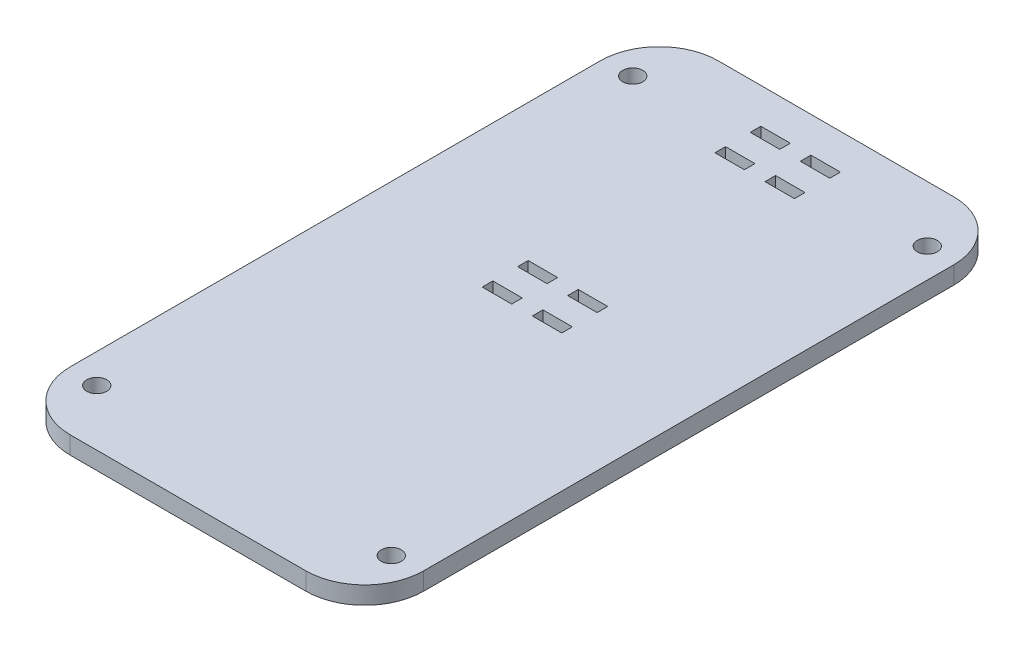
SolidWorks part; units mm, degrees
ref_plane "Front" through (0, 0, 0) normal (0, 0, 1) x (1, 0, 0)
ref_plane "Top" through (0, 0, 0) normal (0, 1, 0) x (1, 0, 0)
ref_plane "Right" through (0, 0, 0) normal (1, 0, 0) x (0, 0, -1)
sketch "Sketch1" plane through (0, 0, 0) normal (0, 1, 0) x (1, 0, 0)
  line L1 (-30, -55) -> (30, -55)
  line L2 (-30, -55) -> (-30, 55)
  line L3 (-30, 55) -> (30, 55)
  line L4 (30, -55) -> (30, 55)
  line L5 (-30, -55) -> (30, 55) construction
  line L6 (-30, 55) -> (30, -55) construction
  point P0 (0, 0)
  dimension "D1" = 60
  dimension "D2" = 110
extrude "Boss-Extrude1" add sketch "Sketch1" along normal blind 3
fillet "Fillet2" radius 10 4 edges at (-30, 1.5, 55) (30, 1.5, 55) (30, 1.5, -55) (-30, 1.5, -55)
sketch "Sketch2" plane through (0, 3, 0) normal (0, 1, 0) x (1, 0, 0)
  line L1 (-13, 31.5649) -> (13, 31.5649) construction
  line L2 (-13, 31.5649) -> (-13, -43.4351) construction
  line L3 (-13, -43.4351) -> (13, -43.4351) construction
  line L4 (13, 31.5649) -> (13, -43.4351) construction
  line L5 (-13, 31.5649) -> (13, -43.4351) construction
  line L6 (-13, -43.4351) -> (13, 31.5649) construction
  circle A0 centre (-13, -43.4351) radius 4.625 construction
  circle A1 centre (-13, 31.5649) radius 4.625
  circle A2 centre (13, 31.5649) radius 4.625
  circle A3 centre (-13, -43.4351) radius 4.625
  circle A4 centre (13, -43.4351) radius 4.625
  point P0 (0, -5.9351)
  dimension "D2" = 9.25
  dimension "D1" = 75
extrude "Cut-Extrude1" [suppressed] cut sketch "Sketch2" against normal through all
sketch "Sketch3" [suppressed] plane through (0, 3, 0) normal (0, 1, 0) x (1, 0, 0)
  circle A0 centre (13, 31.5649) radius 7.5
  circle A1 centre (-13, 31.5649) radius 7.5
  circle A2 centre (-13, -43.4351) radius 7.5
  circle A3 centre (13, -43.4351) radius 7.5
  circle A4 centre (-13, 31.5649) radius 4.625 construction
  circle A5 centre (13, 31.5649) radius 4.625 construction
  dimension "D1" = 15
extrude "Cut-Extrude2" [suppressed] cut sketch "Sketch3" against normal blind 1
hole_wizard "M3 Clearance Hole1" positions "Sketch5" profile "Sketch4" hole size "M3" standard "ANSI Metric" end condition through all
sketch "Sketch5" plane through (0, 3, 0) normal (0, 1, 0) x (1, 0, 0)
  line L1 (-25, -45.5) -> (25, -45.5)
  line L2 (-25, -45.5) -> (-25, 45.5)
  line L3 (-25, 45.5) -> (25, 45.5)
  line L4 (25, -45.5) -> (25, 45.5)
  line L5 (-25, -45.5) -> (25, 45.5) construction
  line L6 (-25, 45.5) -> (25, -45.5) construction
  point P1 (0, 0)
  point P2 (25, 45.5)
  point P371 (-25, -45.5)
  point P372 (-25, 45.5)
  point P373 (25, -45.5)
  dimension "D1" = 50
  dimension "D2" = 91
sketch "Sketch4" plane through (0, 3, 0) normal (1, 0, 0) x (0, 0, 1)
  line L0 (0, 0) -> (0, 3)
  line L1 (0, 3) -> (1.7, 3)
  line L2 (1.7, 3) -> (1.7, 0)
  line L5 (1.7, 0) -> (0, 0)
  line L11 (0, -6.35) -> (0, 107.95) construction
  dimension "Thru Hole Dia." = 3.4
  dimension "Thru Hole Depth" = 3
other "DeleteFace1" face at (0, 0, 1.7) and patch yes
sketch "Sketch6" plane through (0, 3, 0) normal (0, 1, 0) x (1, 0, 0)
  line L0 (-1.75, 41.2) -> (1.75, 41.2) construction
  line L1 (0, 0) -> (0, 41.2) construction
  line L2 (20, 55) -> (-20, 55) construction
  line B0 (-6.75, 3.5) -> (-6.75, 1.7)
  line B1 (-1.75, 3.5) -> (-6.75, 3.5)
  line B2 (-1.75, 1.7) -> (-1.75, 3.5)
  line B3 (-6.75, 1.7) -> (-1.75, 1.7)
  line B4 (6.75, 1.7) -> (6.75, 3.5)
  line B5 (1.75, 1.7) -> (6.75, 1.7)
  line B6 (1.75, 3.5) -> (1.75, 1.7)
  line B7 (6.75, 3.5) -> (1.75, 3.5)
  line B8 (6.75, 7.7) -> (6.75, 9.5)
  line B9 (1.75, 7.7) -> (6.75, 7.7)
  line B10 (1.75, 9.5) -> (1.75, 7.7)
  line B11 (6.75, 9.5) -> (1.75, 9.5)
  line B12 (-6.75, 9.5) -> (-6.75, 7.7)
  line B13 (-1.75, 9.5) -> (-6.75, 9.5)
  line B14 (-1.75, 7.7) -> (-1.75, 9.5)
  line B15 (-6.75, 7.7) -> (-1.75, 7.7)
  line B16 (-6.75, 43) -> (-6.75, 41.2)
  line B17 (-1.75, 43) -> (-6.75, 43)
  line B18 (-1.75, 41.2) -> (-1.75, 43)
  line B19 (-6.75, 41.2) -> (-1.75, 41.2)
  line B20 (-6.75, 49) -> (-6.75, 47.2)
  line B21 (-1.75, 49) -> (-6.75, 49)
  line B22 (-1.75, 47.2) -> (-1.75, 49)
  line B23 (-6.75, 47.2) -> (-1.75, 47.2)
  line B24 (6.75, 47.2) -> (6.75, 49)
  line B25 (1.75, 47.2) -> (6.75, 47.2)
  line B26 (1.75, 49) -> (1.75, 47.2)
  line B27 (6.75, 49) -> (1.75, 49)
  line B28 (6.75, 43) -> (1.75, 43)
  line B29 (6.75, 41.2) -> (6.75, 43)
  line B30 (1.75, 41.2) -> (6.75, 41.2)
  line B31 (1.75, 43) -> (1.75, 41.2)
  dimension "D1" = 6
sketch_block_instance "Block-Mobius Mount-1"
sketch_block "Block-Mobius Mount"
extrude "Cut-Extrude3" cut sketch "Sketch6" against normal through all
